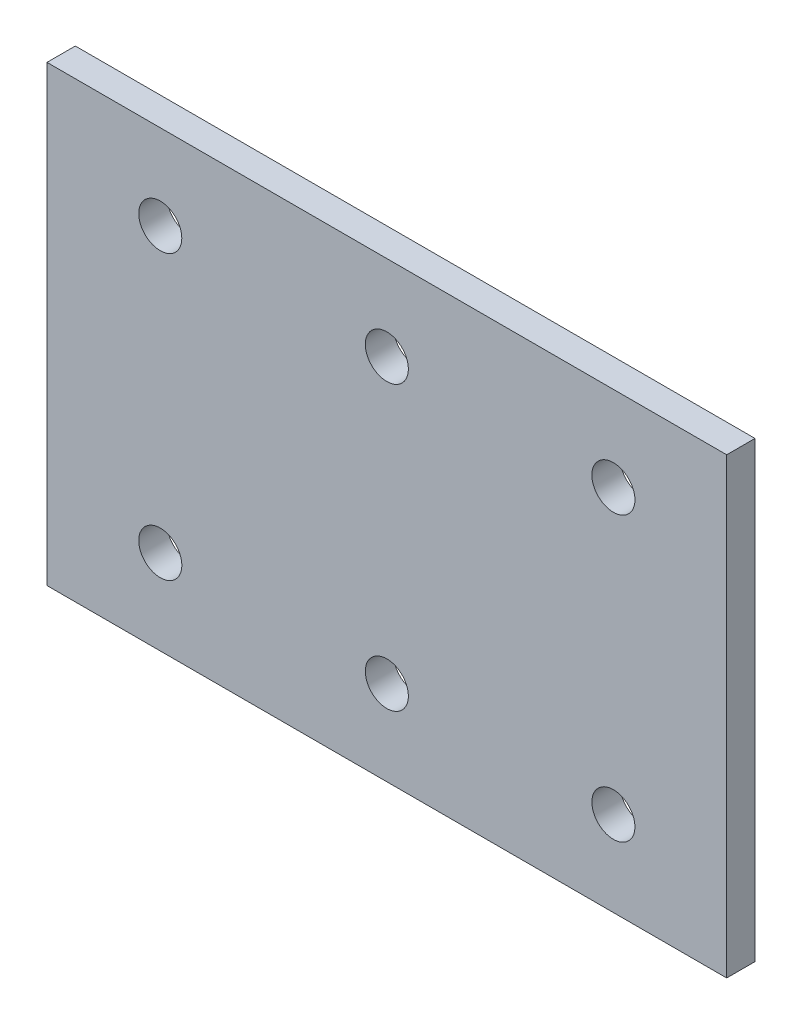
SolidWorks part; units mm, degrees
ref_plane "Front Plane" through (0, 0, 0) normal (0, 0, 1) x (1, 0, 0)
ref_plane "Top Plane" through (0, 0, 0) normal (0, 1, 0) x (1, 0, 0)
ref_plane "Right Plane" through (0, 0, 0) normal (1, 0, 0) x (0, 0, -1)
sketch "Sketch1" plane through (0, 0, 0) normal (0, 0, 1) x (1, 0, 0)
  line L0 (38.1, 50.8) -> (38.1, 0) construction
  line L1 (0, 0) -> (76.2, 0)
  line L2 (0, 0) -> (0, 50.8)
  line L3 (0, 50.8) -> (76.2, 50.8)
  line L4 (76.2, 0) -> (76.2, 50.8)
  line L5 (0, 25.4) -> (76.2, 25.4) construction
  line L6 (12.7, 9.525) -> (12.7, 0) construction
  circle A0 centre (12.7, 41.275) radius 2.413
  circle A1 centre (38.1, 41.275) radius 2.413
  circle A2 centre (63.5, 41.275) radius 2.413
  circle A3 centre (63.5, 9.525) radius 2.413
  circle A4 centre (38.1, 9.525) radius 2.413
  circle A5 centre (12.7, 9.525) radius 2.413
  dimension "D3" = 4.826
  dimension "D1" = 50.8
  dimension "D2" = 76.2
  dimension "D4" = 12.7
  dimension "D6" = 9.525
  dimension "D5" = 3
extrude "Boss-Extrude1" add sketch "Sketch1" along normal blind 3.175
